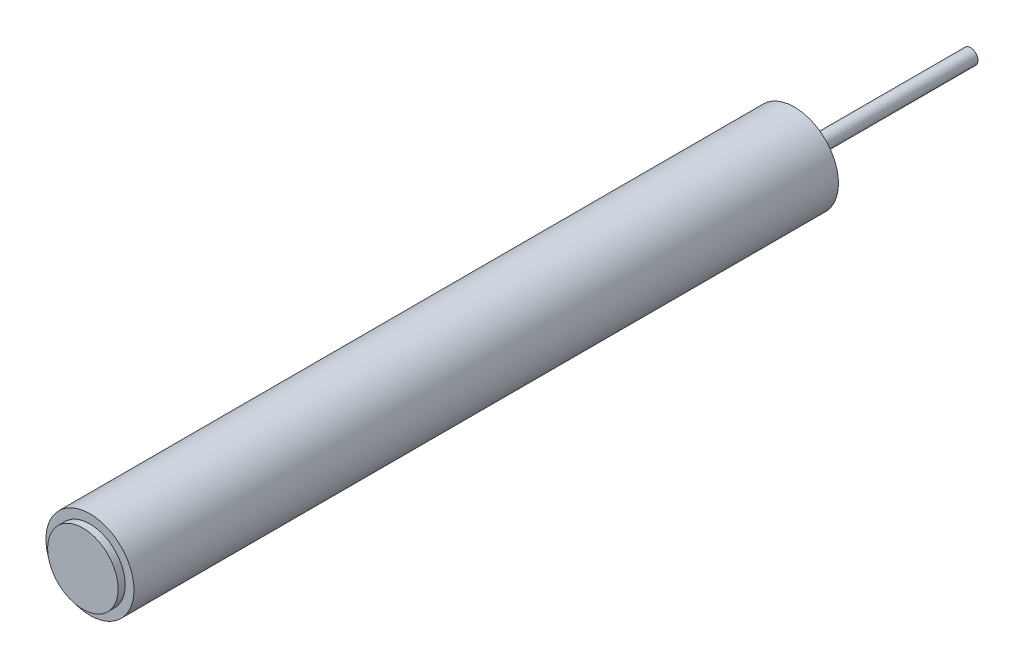
SolidWorks part; units mm, degrees
ref_plane "Front Plane" through (0, 0, 0) normal (0, 0, 1) x (1, 0, 0)
ref_plane "Top Plane" through (0, 0, 0) normal (0, 1, 0) x (1, 0, 0)
ref_plane "Right Plane" through (0, 0, 0) normal (1, 0, 0) x (0, 0, -1)
sketch "Sketch1" plane through (0, 0, 0) normal (0, 0, 1) x (1, 0, 0)
  circle A0 centre (0, 0) radius 3.175
  circle A1 centre (0, 0) radius 2.54
  dimension "D1" = 6.35
  dimension "D2" = 5.08
extrude "Boss-Extrude1" add sketch "Sketch1" along normal blind 50.8
sketch "Sketch2" plane through (0, 0, 50.8) normal (0, 0, 1) x (1, 0, 0)
  circle A0 centre (0, 0) radius 2.54
extrude "Boss-Extrude2" add sketch "Sketch2" against normal blind 2.54 and the other way blind 0.508
ref_plane "Plane1" through (0, 0, 0) normal (0, 0, -1) x (-1, 0, 0)
sketch "Sketch3" plane through (0, 0, 0) normal (0, 0, -1) x (-1, 0, 0)
  circle A0 centre (0, 0) radius 0.5371
extrude "Boss-Extrude3" add sketch "Sketch3" along normal blind 60.96 from surface starting at face at (2.54, 0, 48.26)
